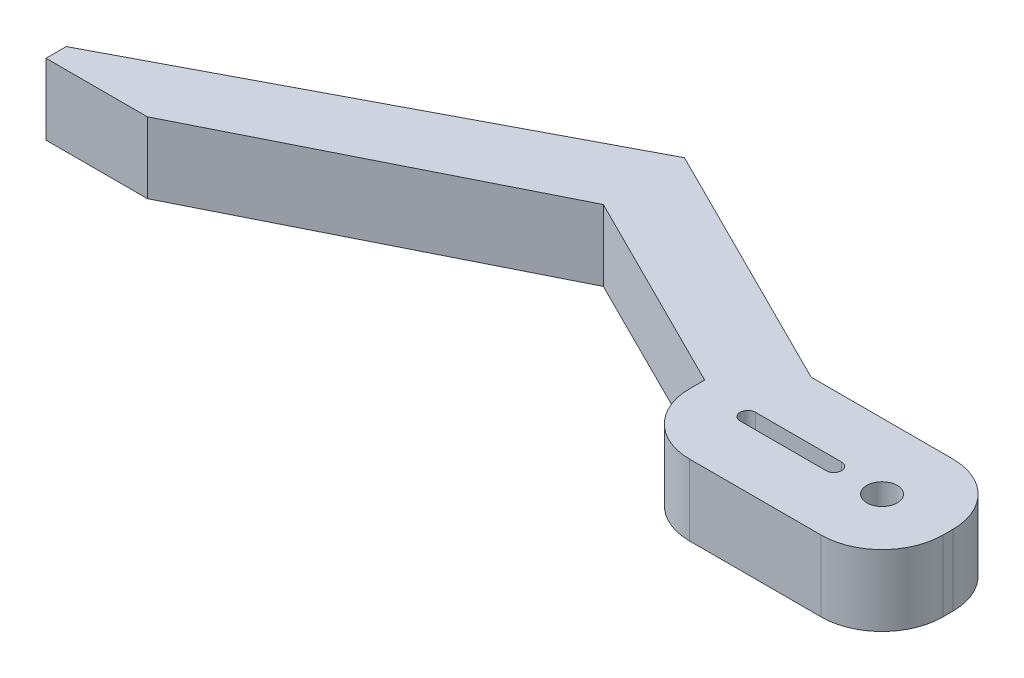
SolidWorks part; units mm, degrees
ref_plane "Front Plane" through (0, 0, 0) normal (0, 0, 1) x (1, 0, 0)
ref_plane "Top Plane" through (0, 0, 0) normal (0, 1, 0) x (1, 0, 0)
ref_plane "Right Plane" through (0, 0, 0) normal (1, 0, 0) x (0, 0, -1)
sketch "Sketch1" plane through (0, 0, 0) normal (0, 1, 0) x (1, 0, 0)
  line L0 (0, 0) -> (-30, 0)
  line L1 (0, 0) -> (0, 15)
  line L2 (0, 0) -> (30, 0)
  line L3 (-30, 0) -> (0, 15)
  line L4 (0, 15) -> (30, 0)
  line L5 (-30, 0) -> (-40, 0)
  line L6 (-40, 0) -> (-40, 2)
  line L7 (-40, 2) -> (0, 23)
  line L8 (0, 23) -> (30, 8)
  line L9 (45, 10.5) -> (45, -2.5)
  line L13 (45, -2.5) -> (20, -2.5)
  line L14 (20, -2.5) -> (20, 10.5)
  line L15 (20, 10.5) -> (45, 10.5)
  point P10 (45, 4)
  dimension "D1" = 30
  dimension "D2" = 15
  dimension "D3" = 30
  dimension "D4" = 10
  dimension "D5" = 2
  dimension "D6" = 8
  dimension "D7" = 0
  dimension "D8" = 8
  dimension "D9" = 4
  dimension "D10" = 13
  dimension "D12" = 25
extrude "Boss-Extrude1" add sketch "Sketch1" along normal blind 7 contours L8 L7 L6 L5 L3 L4 | L15 L9 L13 L14 region at (-7.2852, 0, -11.4353)
hole_wizard "Ø3.0 (3) Diameter Hole3" positions "Sketch9" profile "Sketch10" hole size "Ø3.0" standard "ISO" end condition through all
sketch "Sketch9" plane through (0, 7, 0) normal (0, 1, 0) x (1, 0, 0)
  line L0 (45, 10.5) -> (45, -2.5) construction
  line L1 (25, 10.5) -> (45, 10.5) construction
  point P0 (38.5, 4)
  point P5 (45, 4)
  dimension "D1" = 6.5
  dimension "D2" = 6.5
sketch "Sketch10" plane through (38.5, 7, -4) normal (1, 0, 0) x (0, 0, 1)
  line L0 (0, 0) -> (0, 7)
  line L1 (0, 7) -> (1.5, 7)
  line L2 (1.5, 7) -> (1.5, 0)
  line L5 (1.5, 0) -> (0, 0)
  line L11 (0, -6.35) -> (0, 107.95) construction
  dimension "Thru Hole Dia." = 3
  dimension "Thru Hole Depth" = 7
fillet "Fillet7" radius 6 3 edges at (20, 3.5, 2.5) (45, 3.5, -10.5) (45, 3.5, 2.5)
sketch "Sketch11" plane through (0, 7, 0) normal (0, 1, 0) x (1, 0, 0)
  line L0 (38.5, 4) -> (34.5, 4)
  line L1 (34.5, 4) -> (24.5, 4)
  line L2 (24.5, 4) -> (24.5, 3.25)
  line L3 (24.5, 3.25) -> (34.5, 3.25)
  line L4 (34.5, 3.25) -> (34.5, 4.75)
  line L5 (34.5, 4.75) -> (24.5, 4.75)
  line L6 (24.5, 4.75) -> (24.5, 4)
  dimension "D1" = 1.5
  dimension "D2" = 0.75
  dimension "D3" = 4
  dimension "D4" = 10
extrude "Cut-Extrude1" cut sketch "Sketch11" against normal through all contours L2 L3 L4 L5 L6
fillet "Fillet8" radius 0.75 4 edges at (34.5, 3.5, -3.25) (34.5, 3.5, -4.75) (24.5, 3.5, -4.75) (24.5, 3.5, -3.25)
